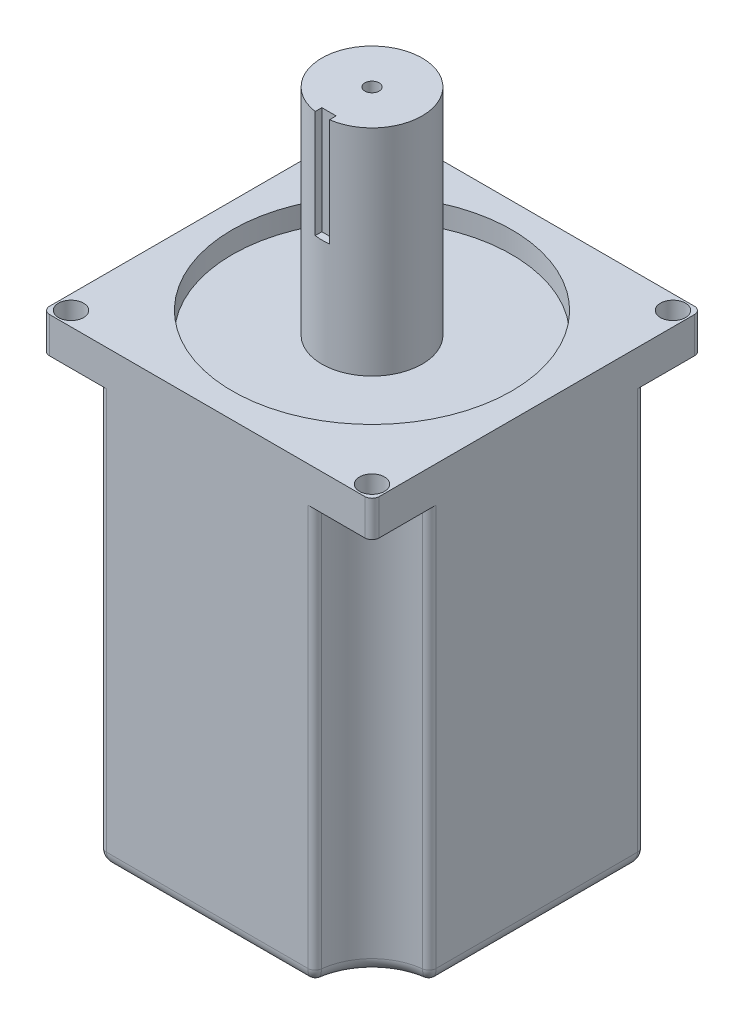
SolidWorks part; units mm, degrees
ref_plane "Front Plane" through (0, 0, 0) normal (0, 0, 1) x (1, 0, 0)
ref_plane "Top Plane" through (0, 0, 0) normal (0, 1, 0) x (1, 0, 0)
ref_plane "Right Plane" through (0, 0, 0) normal (1, 0, 0) x (0, 0, -1)
sketch "Sketch1" plane through (0, 0, 0) normal (0, 1, 0) x (1, 0, 0)
  line L1 (-23, 23) -> (23, 23)
  line L2 (-23, 23) -> (-23, -23)
  line L3 (-23, -23) -> (23, -23)
  line L4 (23, 23) -> (23, -23)
  line L5 (-23, 23) -> (23, -23) construction
  line L6 (-23, -23) -> (23, 23) construction
  point P0 (0, 0)
  dimension "D1" = 46
  dimension "D2" = 46
extrude "Boss-Extrude1" add sketch "Sketch1" along normal blind 58
sketch "Sketch2" plane through (0, 0, 0) normal (0, 0, 1) x (1, 0, 0)
  line L0 (0, 58) -> (0, 95.0525) construction
  line L1 (-23, 58) -> (23, 58) construction
  line L2 (0, 58) -> (0, 90) construction
  line L3 (0, 90) -> (7, 90)
  line L4 (7, 90) -> (7, 60)
  line L5 (7, 60) -> (19.5, 60)
  line L6 (19.5, 60) -> (19.5, 63)
  line L7 (19.5, 63) -> (23, 63)
  line L8 (23, 63) -> (23, 58)
  line L9 (23, 58) -> (0, 58)
  line L10 (0, 58) -> (0, 90)
  dimension "D1" = 32
  dimension "D2" = 14
  dimension "D3" = 2
  dimension "D4" = 3
  dimension "D5" = 3.5
revolve "Revolve1" add sketch "Sketch2" angle 360 about L10
sketch "Sketch3" plane through (0, 58, 0) normal (0, 1, 0) x (1, 0, 0)
  line L2 (23, -23) -> (23, 0)
  line L3 (0, -23) -> (23, -23)
  line L4 (23, -23) -> (23, 0)
  line L5 (0, -23) -> (23, -23)
  line L6 (-23, -23) -> (0, -23)
  line L7 (-23, 0) -> (-23, -23)
  line L8 (-23, -23) -> (0, -23)
  line L9 (-23, 0) -> (-23, -23)
  line L10 (-23, 23) -> (-23, 0)
  line L11 (0, 23) -> (-23, 23)
  line L12 (-23, 23) -> (-23, 0)
  line L13 (0, 23) -> (-23, 23)
  line L14 (23, 23) -> (0, 23)
  line L15 (23, 0) -> (23, 23)
  line L16 (23, 23) -> (0, 23)
  line L17 (23, 0) -> (23, 23)
  circle A0 centre (0, 0) radius 23 construction
  arc A1 (0, -23) -> (23, 0) centre (0, 0) ccw
  arc A3 (-23, 0) -> (0, -23) centre (0, 0) ccw
  arc A5 (0, 23) -> (-23, 0) centre (0, 0) ccw
  arc A7 (23, 0) -> (0, 23) centre (0, 0) ccw
  arc A8 (0, 23) -> (-23, 0) centre (0, 0) ccw construction
  circle A9 centre (0, 0) radius 23
  arc A10 (0, 23) -> (-23, 0) centre (0, 0) ccw
  line M13 (23, -23) -> (23, 0)
  arc M14 (23, 0) -> (0, -23) centre (0, 0) cw
  line M15 (0, -23) -> (23, -23)
  dimension "D1" = 0
  dimension "D2" = 0
  dimension "D3" = 0
  dimension "D4" = 0
extrude "Boss-Extrude2" add sketch "Sketch3" along direction (0, 1, 0) on the side of the normal blind 5 contours M15 M13 M14 | A9 L17 L16 | A9 L9 L8 | A9 L13 L12 region at (17.8625, 58, 17.8625) region at (17.8625, 58, -17.8625) region at (-17.8625, 58, 17.8625) region at (-17.8625, 58, -17.8625)
sketch "Sketch4" plane through (0, 0, 0) normal (0, -1, 0) x (1, 0, 0)
  circle A0 centre (-23, -23) radius 8
  circle A1 centre (23, -23) radius 8
  circle A2 centre (23, 23) radius 8
  circle A3 centre (-23, 23) radius 8
  dimension "D1" = 16
extrude "Cut-Extrude1" cut sketch "Sketch4" against normal blind 58
fillet "Fillet1" radius 2 8 edges at (23, 0, 0) (0, 0, -23) (-23, 0, 0) (0, 0, 23) (-17.3431, 0, 17.3431) (-17.3431, 0, -17.3431) (17.3431, 0, -17.3431) (17.3431, 0, 17.3431) type face fillet first side face at (0, 0, 0) second side face at (18.1716, 29, -18.1716) second side face at (23, 44.75, 0) second side face at (18.1716, 29, 18.1716) second side face at (0, 44.75, 23) second side face at (-18.1716, 29, 18.1716) second side face at (-23, 44.75, 0) second side face at (-18.1716, 29, -18.1716) second side face at (0, 44.75, -23)
fillet "Fillet2" radius 1 16 edges at (-22.7371, 1.0088, 14.7413) (-22.7371, 1.0088, -14.7413) (-14.7413, 1.0088, -22.7371) (14.7413, 1.0088, -22.7371) (22.7371, 1.0088, -14.7413) (-14.7413, 1.0088, 22.7371) (22.7371, 1.0088, 14.7413) (14.7413, 1.0088, 22.7371) (-23, 30, 15) (-23, 30, -15) (-15, 30, -23) (15, 30, -23) (23, 30, -15) (-15, 30, 23) (23, 30, 15) (15, 30, 23)
fillet "Fillet3" radius 1 4 edges at (-23, 60.5, 23) (-23, 60.5, -23) (23, 60.5, -23) (23, 60.5, 23)
sketch "Sketch5" plane through (0, 0, 0) normal (1, 0, 0) x (0, 0, -1)
  line L0 (0, 0) -> (0, 105.6657) construction
  line L1 (-22, 63) -> (22, 63) construction
  line L2 (0, 2.8) -> (20, 2.8)
  line L3 (0, 2.8) -> (0, 56.5)
  line L4 (0, 56.5) -> (20, 56.5)
  line L5 (20, 2.8) -> (20, 56.5)
  line L6 (23, 58) -> (23, 2) construction
  line L7 (13.202, 0) -> (21, 0) construction
  dimension "D1" = 6.5
  dimension "D2" = 3
  dimension "D3" = 2.8
revolve "Cut-Revolve1" cut sketch "Sketch5" angle 360 about L0
sketch "Sketch6" plane through (0, 58, 0) normal (0, -1, 0) x (1, 0, 0)
  line L1 (-21, -21) -> (21, -21) construction
  line L2 (-21, -21) -> (-21, 21) construction
  line L3 (-21, 21) -> (21, 21) construction
  line L4 (21, -21) -> (21, 21) construction
  line L5 (-21, -21) -> (21, 21) construction
  line L6 (-21, 21) -> (21, -21) construction
  circle A0 centre (21, 21) radius 1.75
  circle A4 centre (21, -21) radius 1.75
  circle A5 centre (-21, -21) radius 1.75
  circle A6 centre (-21, 21) radius 1.75
  point P0 (0, 0)
  point P7 (-21.1504, 21)
  point P20 (0, -1)
  point P21 (0, 0)
  dimension "D1" = 3.5
  dimension "D2" = 42
  dimension "D3" = 42
  dimension "D4" = 4
extrude "Cut-Extrude2" cut sketch "Sketch6" against normal through all
hole_wizard "Ø2.0mm Dowel Hole1" positions "Sketch7" profile "Sketch8" hole size "Ø2.0" standard "ISO"
sketch "Sketch7" plane through (0, 90, 0) normal (0, 1, 0) x (1, 0, 0)
  point P0 (0, 0)
sketch "Sketch8" plane through (0, 90, 0) normal (1, 0, 0) x (0, 0, 1)
  line L0 (0, 0) -> (0, 8.6009)
  line L1 (0, 8.6009) -> (1, 8)
  line L2 (1, 8) -> (1, 0)
  line L5 (1, 0) -> (0, 0)
  line L10 (0, 8.6009) -> (-1, 8) construction
  line L11 (0, -6.35) -> (0, 107.95) construction
  dimension "Hole Dia." = 2
  dimension "Hole Depth" = 8
  dimension "Drill Angle" = 118
sketch "Sketch9" plane through (0, 90, 0) normal (0, 1, 0) x (1, 0, 0)
  line L1 (-1, -6) -> (1, -6)
  line L2 (-1, -6) -> (-1, -8)
  line L3 (-1, -8) -> (1, -8)
  line L4 (1, -6) -> (1, -8)
  line L5 (-1, -6) -> (1, -8) construction
  line L6 (-1, -8) -> (1, -6) construction
  circle A0 centre (0, 0) radius 7 construction
  circle A1 centre (0, 0) radius 7 construction
  point P0 (0, -7)
  dimension "D1" = 2
  dimension "D2" = 2
extrude "Cut-Extrude3" cut sketch "Sketch9" against normal blind 15
